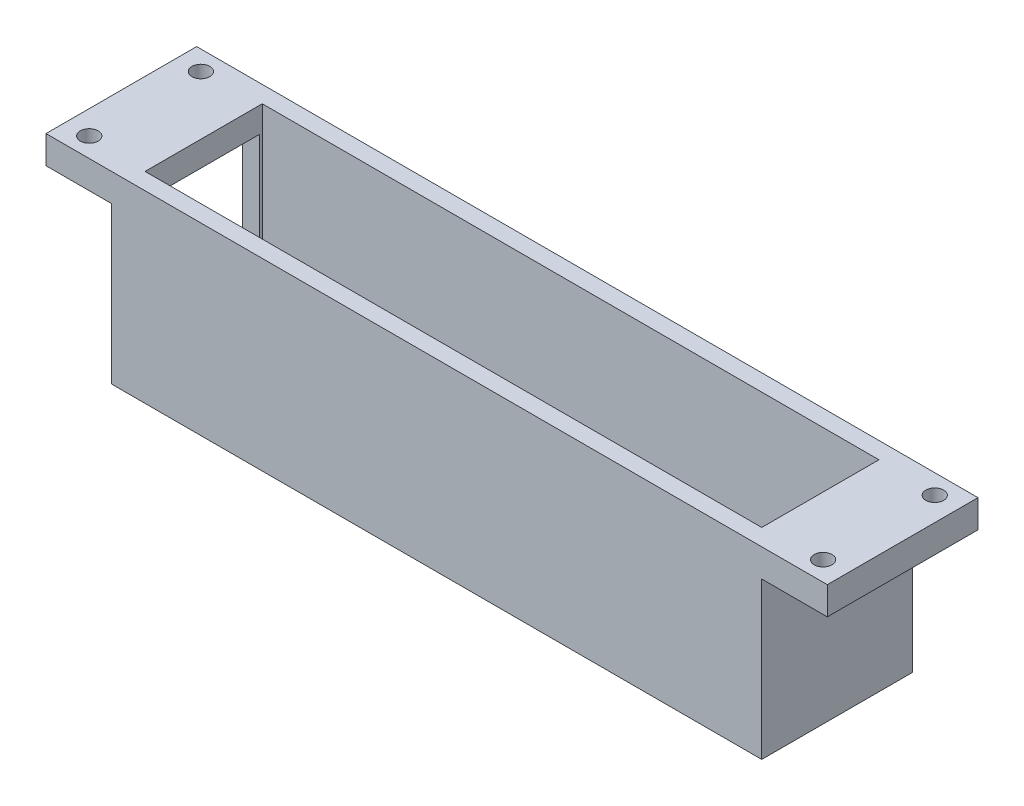
SolidWorks part; units mm, degrees
ref_plane "Płaszczyzna przednia" through (0, 0, 0) normal (0, 0, 1) x (1, 0, 0)
ref_plane "Płaszczyzna górna" through (0, 0, 0) normal (0, 1, 0) x (1, 0, 0)
ref_plane "Płaszczyzna prawa" through (0, 0, 0) normal (1, 0, 0) x (0, 0, -1)
sketch "Szkic1" plane through (0, 0, 0) normal (0, 0, 1) x (1, 0, 0)
  line L1 (0, 0) -> (116.5, 0)
  line L2 (0, 0) -> (0, 28)
  line L4 (116.5, 0) -> (116.5, 28)
  line L5 (-11.75, 33) -> (-11.75, 28)
  line L6 (-11.75, 28) -> (0, 28)
  line L8 (128.25, 33) -> (128.25, 28)
  line L9 (128.25, 28) -> (116.5, 28)
  line L10 (128.25, 33) -> (-11.75, 33)
  dimension "D1" = 116.5
  dimension "D2" = 140
  dimension "D4" = 28
  dimension "D5" = 5
  dimension "D6" = 5
extrude "Dodanie-wyciągnięcie1" add sketch "Szkic1" along normal blind 27
sketch "Szkic2" plane through (0, 33, 0) normal (0, 1, 0) x (1, 0, 0)
  line L0 (128.25, 0) -> (-11.75, 0) construction
  line L1 (3, -3) -> (113.5, -3)
  line L2 (3, -3) -> (3, -24)
  line L3 (3, -24) -> (113.5, -24)
  line L4 (113.5, -3) -> (113.5, -24)
  line L6 (58.25, 0) -> (58.25, -27) construction
  line L7 (128.25, -27) -> (-11.75, -27) construction
  line L8 (58.25, -3) -> (58.25, -24) construction
  dimension "D1" = 21
  dimension "D2" = 110.5
  dimension "D3" = 3
extrude "Wytnij-wyciągnięcie1" cut sketch "Szkic2" against normal offset from surface (30 mm away) 3 up to face at (58.25, 0, 13.5)
sketch "Szkic3" plane through (116.5, 0, 0) normal (1, 0, 0) x (0, 0, -1)
  line L0 (-27, 0) -> (-27, 28) construction
  line L1 (-23.4, 26) -> (-3.4, 26)
  line L2 (-23.4, 26) -> (-23.4, 11)
  line L3 (-23.4, 11) -> (-3.4, 11)
  line L4 (-3.4, 26) -> (-3.4, 11)
  line L5 (-27, 0) -> (0, 0) construction
  dimension "D1" = 20
  dimension "D2" = 15
  dimension "D3" = 3.6
  dimension "D4" = 11
sketch "Szkic4" plane through (0, 0, 0) normal (-1, 0, 0) x (0, 0, 1)
  line L0 (27, 0) -> (0, 0) construction
  line L1 (3.5, 28.5) -> (24, 28.5)
  line L2 (3.5, 28.5) -> (3.5, 8.5)
  line L3 (3.5, 8.5) -> (24, 8.5)
  line L4 (24, 28.5) -> (24, 8.5)
  line L5 (0, 28) -> (0, 0) construction
  dimension "D1" = 20.5
  dimension "D2" = 20
  dimension "D3" = 8.5
  dimension "D4" = 3.5
extrude "Wytnij-wyciągnięcie3" cut sketch "Szkic4" against normal blind 3
sketch "Szkic5" plane through (0, 33, 0) normal (0, 1, 0) x (1, 0, 0)
  line L0 (128.25, 0) -> (-11.75, 0) construction
  line L1 (-11.75, -27) -> (-11.75, 0) construction
  line L2 (128.25, -27) -> (128.25, 0) construction
  circle A0 centre (-7.5, -3.5) radius 1.6
  circle A1 centre (124, -3.5) radius 1.6
  circle A2 centre (124, -23.5) radius 1.6
  circle A3 centre (-7.5, -23.5) radius 1.6
  point P6 (121.9311, -24.3208)
  point P15 (124.5, -24)
  dimension "D1" = 3.2
  dimension "D3" = 4.25
  dimension "D6" = 20
  dimension "D7" = 4.25
  dimension "D8" = 4.25
  dimension "D2" = 3.5
  dimension "D4" = 2
  dimension "D5" = 2
extrude "Wytnij-wyciągnięcie4" cut sketch "Szkic5" against normal through all
